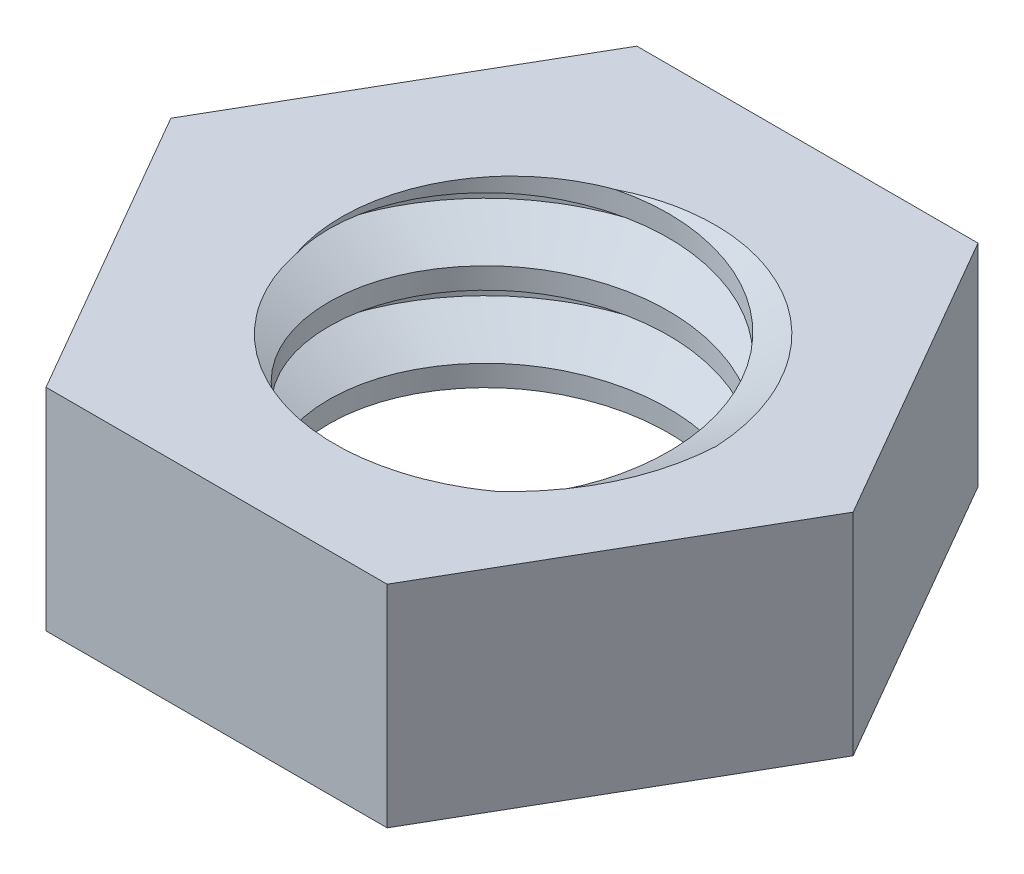
SolidWorks part; units mm, degrees
ref_plane "Front Plane" through (0, 0, 0) normal (0, 0, 1) x (1, 0, 0)
ref_plane "Top Plane" through (0, 0, 0) normal (0, 1, 0) x (1, 0, 0)
ref_plane "Right Plane" through (0, 0, 0) normal (1, 0, 0) x (0, 0, -1)
sketch "Sketch1" plane through (0, 0, 0) normal (0, 1, 0) x (1, 0, 0)
  line L0 (-90.4875, 0) -> (0, 0) construction
  line L14 (5.1326, 8.89) -> (-5.1326, 8.89)
  line L15 (-5.1326, 8.89) -> (-10.2653, 0)
  line L16 (-10.2653, 0) -> (-5.1326, -8.89)
  line L17 (-5.1326, -8.89) -> (5.1326, -8.89)
  line L18 (5.1326, -8.89) -> (10.2653, 0)
  line L19 (10.2653, 0) -> (5.1326, 8.89)
  circle A3 centre (0, 0) radius 6.5
  circle A6 centre (0, 0) radius 8.89 construction
  dimension "D2" = 13
  dimension "D11" = 8.89
extrude "Boss-Extrude1" add sketch "Sketch1" along normal blind 6.35 contours A3 region at (7.4638, 0, -4.3092)
thread "Thread1" pitch 2.54 method extrude profile "Thread Profile1" start angle 3, offset 3.81, length 15.08, pitch 2.54, diameter 13
ref_plane "Plane1" through (-6.4911, 10.16, -0.3402) normal (-0.0523, 0, 0.9986) x (-0.9986, 0, -0.0523)
sketch "Thread Profile1" plane through (-6.4911, 10.16, -0.3402) normal (-0.0523, 0, 0.9986) x (-0.9986, 0, -0.0523)
  line L0 (0, 0) -> (0, 2.54) construction
  line L11 (0, 0) -> (0, 2.2225)
  line L12 (0, 2.2225) -> (-1.3748, 1.4287)
  line L13 (-1.3748, 1.4287) -> (-1.3748, 0.7937)
  line L15 (-1.3748, 0.7937) -> (0, 0)
  line L17 (-1.3748, 1.1112) -> (0, 1.1112) construction
  point P2 (0, 0)
  dimension "Pitch" = 2.54
  dimension "Profile_Angle" = 60
  dimension "Profile_Land" = 0.635
  dimension "Profile_Height" = 1.3748
sketch "Sketch25" plane through (7.699, 0, -4.445) normal (0.866, 0, -0.5) x (-0.5, 0, -0.866)
  line L0 (-5.1326, 6.35) -> (5.1326, 6.35) construction
  line L1 (-9.3289, 6.35) -> (8.9735, 6.35)
  line L2 (-5.1326, 0) -> (5.1326, 0) construction
  line L3 (-9.0623, 0) -> (8.9291, 0)
  line L4 (-9.0623, 0) -> (-9.0623, -7.9762)
  line L5 (-9.0623, -7.9762) -> (8.9291, -7.9762)
  line L6 (8.9291, -7.9762) -> (8.9291, 0)
  line L7 (-9.3289, 6.35) -> (-9.3289, 16.5179)
  line L8 (-9.3289, 16.5179) -> (8.9735, 16.5179)
  line L9 (8.9735, 16.5179) -> (8.9735, 6.35)
extrude "Cut-Extrude1" cut sketch "Sketch25" against normal through all
